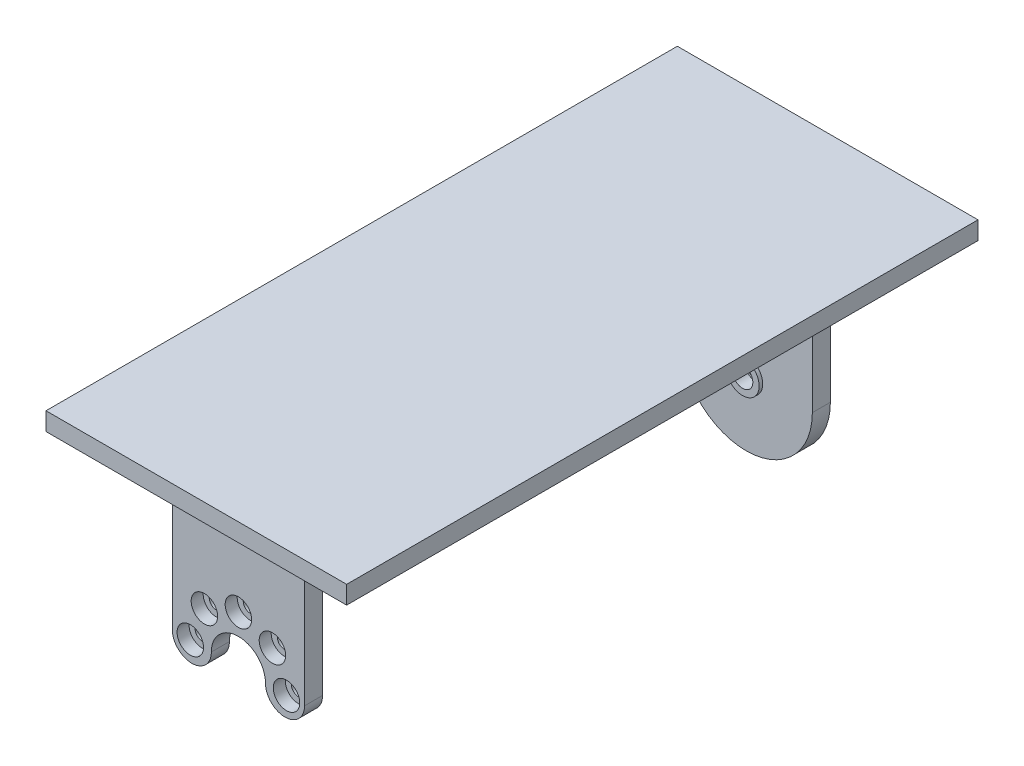
SolidWorks part; units mm, degrees
ref_plane "Plano frontal" through (0, 0, 0) normal (0, 0, 1) x (1, 0, 0)
ref_plane "Plano superior" through (0, 0, 0) normal (0, 1, 0) x (1, 0, 0)
ref_plane "Plano direito" through (0, 0, 0) normal (1, 0, 0) x (0, 0, -1)
sketch "Esboço1" plane through (0, 0, 0) normal (0, 0, 1) x (1, 0, 0)
  line L0 (11, 0) -> (11, 25)
  line L1 (11, 25) -> (-11, 25)
  line L2 (-11, 25) -> (-11, 0)
  arc A3 (11, 0) -> (4.5, 0) centre (7.75, 0) cw
  arc A8 (4.5, 0) -> (-4.5, 0) centre (0, 0) ccw
  arc A10 (-4.5, 0) -> (-11, 0) centre (-7.75, 0) cw
  dimension "D1" = 25
extrude "Ressalto-extrusão1" add sketch "Esboço1" along normal blind 3
sketch "Esboço2" plane through (0, 25, 0) normal (0, 1, 0) x (1, 0, 0)
  line L1 (-25, -10) -> (25, -10)
  line L2 (-25, -10) -> (-25, 95)
  line L3 (-25, 95) -> (25, 95)
  line L4 (25, -10) -> (25, 95)
  line L5 (11, -3) -> (-11, -3) construction
  point P7 (0, -3)
  point P8 (0, -10)
  dimension "D1" = 105
  dimension "D2" = 50
  dimension "D3" = 7
extrude "Ressalto-extrusão2" add sketch "Esboço2" along normal blind 3
ref_plane "Plano1" through (0, 0, -81.45) normal (0, 0, -1) x (-1, 0, 0)
sketch "Esboço3" plane through (0, 0, -81.45) normal (0, 0, -1) x (-1, 0, 0)
  line L1 (-11, 0) -> (-11, 25)
  line L2 (-11, 25) -> (11, 25)
  line L3 (11, 25) -> (11, 0)
  arc A0 (-11, 0) -> (11, 0) centre (0, 0) ccw
  dimension "D1" = 22
extrude "Ressalto-extrusão3" add sketch "Esboço3" along normal blind 3
hole_wizard "Rebaixo para SHCS M21" positions "Esboço4" profile "Esboço5" counterbore size "M2" standard "Ansi Metric" end condition up to next
sketch "Esboço4" plane through (0, 0, 3) normal (0, 0, 1) x (1, 0, 0)
  arc A0 (8.8, 0) -> (7.2, 0) centre (8, 0) ccw construction
  point P0 (8, 0)
sketch "Esboço5" plane through (8, 0, 3) normal (1, 0, 0) x (0, -1, 0)
  line L0 (0, 0) -> (0, 3)
  line L1 (0, 3) -> (1.2, 3)
  line L3 (1.2, 3) -> (1.2, 2)
  line L4 (1.2, 2) -> (2.2, 2)
  line L5 (2.2, 2) -> (2.2, 0)
  line L7 (2.2, 0) -> (0, 0)
  line L11 (0, -6.35) -> (0, 107.95) construction
  dimension "Thru Hole Dia." = 2.4
  dimension "Thru Hole Depth" = 3
  dimension "C'Bore Dia." = 4.4
  dimension "C'Bore Depth" = 2
pattern_circular "PadrãoCircular1" count 5 over 180 about axis through (0, 0, 3) along (0, 0, -1) of "Rebaixo para SHCS M21" reverse direction yes
sketch "Esboço6" plane through (0, 0, 0) normal (1, 0, 0) x (0, 0, -1)
  line L0 (-10, 25) -> (-3, 25) construction
  line L3 (-3, 25) -> (-3, 18) construction
  line L4 (-3, 0) -> (-3, 25) construction
  line L5 (-3, 18) -> (-10, 25)
rib "Nervura1" sketch "Esboço6" sketch "Esboço6" thickness 15 extrusion direction parallel to sketch draft on no parameters "D1"=15
sketch "Esboço7" plane through (0, 0, 3) normal (0, 0, 1) x (1, 0, 0)
  line L0 (-7.5, 25) -> (7.5, 25) construction
  line L1 (-5, 25) -> (5, 25)
  line L2 (-5, 25) -> (-5, 18)
  line L3 (-5, 18) -> (5, 18)
  line L4 (5, 25) -> (5, 18)
  line L5 (7.5, 18) -> (-7.5, 18) construction
  point P8 (0, 18)
  point P9 (0, 18)
  dimension "D1" = 10
extrude "Corte-extrusão1" cut sketch "Esboço7" along normal up to surface (7 mm away) up to face at (0, 21.5, 6.5)
sketch "Esboço8" plane through (0, 0, 0) normal (1, 0, 0) x (0, 0, -1)
  line L0 (0, 18) -> (7, 25)
  line L1 (0, 0) -> (0, 25) construction
  line L2 (-10, 25) -> (95, 25) construction
  line L5 (-10, 25) -> (-3, 18) construction
rib "Nervura7" sketch "Esboço8" sketch "Esboço8" thickness 15 extrusion direction parallel to sketch draft on no parameters "D1"=15
sketch "Esboço9" plane through (0, 0, 0) normal (0, 0, -1) x (-1, 0, 0)
  line L0 (-7.5, 18) -> (7.5, 18) construction
  line L1 (-5, 18) -> (5, 18)
  line L2 (-5, 18) -> (-5, 25)
  line L3 (-5, 25) -> (5, 25)
  line L4 (5, 18) -> (5, 25)
  line L5 (-11, 25) -> (-7.5, 25) construction
  point P8 (0, 18)
  point P9 (0, 18)
  dimension "D1" = 10
extrude "Corte-extrusão2" cut sketch "Esboço9" along normal up to surface up to face at (0, 21.5, -3.5)
pattern_linear "Padrão linear1" count 2 spacing 84.45 along (0, 0, -1) of "Nervura1", "Nervura7", "Corte-extrusão2", "Corte-extrusão1"
sketch "Esboço10" plane through (0, 0, -81.45) normal (0, 0, 1) x (1, 0, 0)
  circle A0 centre (0, 0) radius 2.75
  circle A2 centre (0, 0) radius 3.25 construction
  dimension "D1" = 0.5
extrude "Ressalto-extrusão4" add sketch "Esboço10" along normal offset from surface (0.6 mm away) 0.25 contours A0
hole_wizard "Rebaixo para parafuso com cabeça panela de M31" positions "Esboço11" profile "Esboço12" counterbore size "M3" standard "DIN" end condition up to next
sketch "Esboço11" plane through (0, 0, -84.45) normal (0, 0, -1) x (-1, 0, 0)
  circle A0 centre (0, 0) radius 3.25 construction
  point P0 (0, 0)
sketch "Esboço12" plane through (0, 0, -84.45) normal (1, 0, 0) x (0, 1, 0)
  line L0 (0, 0) -> (0, 3.6)
  line L1 (0, 3.6) -> (1.7, 3.6)
  line L3 (1.7, 3.6) -> (1.7, 1.5)
  line L4 (1.7, 1.5) -> (3.5, 1.5)
  line L5 (3.5, 1.5) -> (3.5, 0)
  line L7 (3.5, 0) -> (0, 0)
  line L11 (0, -6.35) -> (0, 107.95) construction
  dimension "Thru Hole Dia." = 3.4
  dimension "Thru Hole Depth" = 3.6
  dimension "C'Bore Dia." = 7
  dimension "C'Bore Depth" = 1.5
